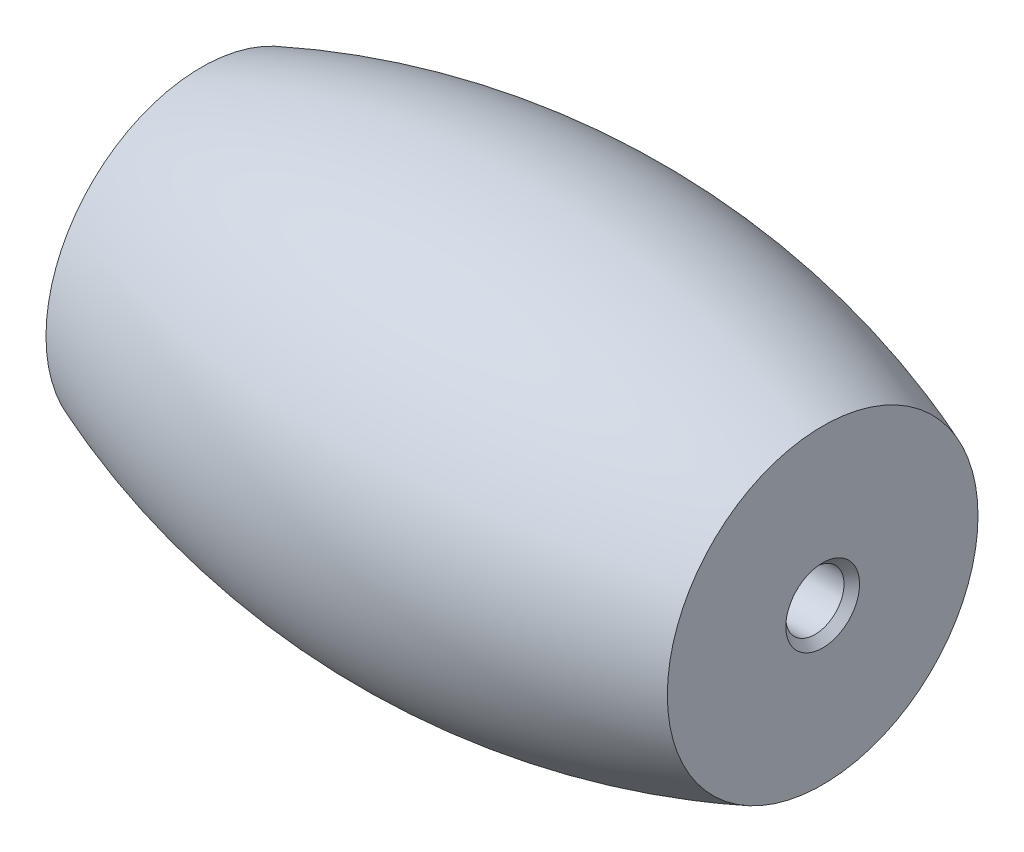
SolidWorks part; units mm, degrees
material "Plastique personnalisé"
ref_plane "Alzado" through (0, 0, 0) normal (0, 0, 1) x (1, 0, 0)
ref_plane "Planta" through (0, 0, 0) normal (0, 1, 0) x (1, 0, 0)
ref_plane "Vista lateral" through (0, 0, 0) normal (1, 0, 0) x (0, 0, -1)
sketch "Croquis1" plane through (0, 0, 0) normal (0, 0, 1) x (1, 0, 0)
  line L5 (-8, 16.5798) -> (8, 16.5798) construction
  line L6 (-8, 20.5798) -> (-8, 16.5798)
  line L7 (-8, 16.5798) -> (8, 16.5798)
  line L8 (8, 16.5798) -> (8, 20.5798)
  arc A0 (8, 20.5798) -> (-8, 20.5798) centre (0, 0) ccw
revolve "Revolución1" add sketch "Croquis1" angle 360 about L5
sketch "Croquis2" plane through (-8, 0, 0) normal (-1, 0, 0) x (0, 0, 1)
  circle A0 centre (0, 16.5798) radius 0.75
  dimension "D1" = 1.5
extrude "Cortar-Extruir1" cut sketch "Croquis2" against normal up to surface (16 mm away) up to face at (8, 16.5798, 4)
chamfer "Chaflán1" distance 0.2 angle 45 2 edges at (8, 16.5798, 0.75) (-8, 16.5798, 0.75)
